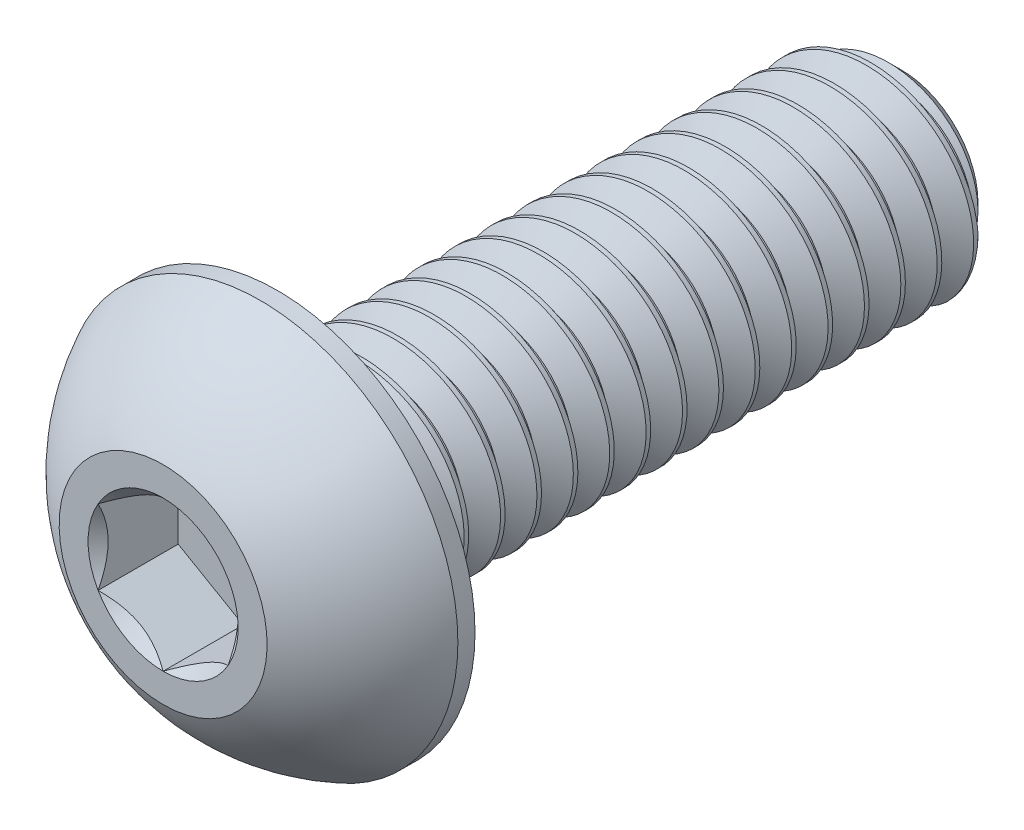
SolidWorks part; units mm, degrees
ref_plane "Front" through (0, 0, 0) normal (0, 0, 1) x (1, 0, 0)
ref_plane "Top" through (0, 0, 0) normal (0, 1, 0) x (1, 0, 0)
ref_plane "Right" through (0, 0, 0) normal (1, 0, 0) x (0, 0, -1)
sketch "Sketch1" plane through (0, 0, 0) normal (1, 0, 0) x (0, 0, -1)
  line L2 (2.2, 2) -> (14.2, 2)
  line L3 (14.2, 2) -> (14.2, 0)
  line L4 (14.2, 0) -> (2.2, 0)
  line L6 (1.87, 3.8) -> (2.2, 3.8) construction
  line L7 (14.2, 2) -> (14.2, -2) construction
  line L8 (0, 0) -> (2.2, 0) construction
  line L9 (2.2, 3.8) -> (2.2, -3.8) construction
  line L11 (2.2, 2) -> (2.2, 0)
  line L13 (0, 1.25) -> (0, -1.25) construction
  line L14 (0, 1.25) -> (0, 2) construction
  line L15 (14.1562, 2.0758) -> (14.5062, 1.4696) construction
  line L16 (14.5062, 1.4696) -> (14.8562, 2.0758) construction
  line L17 (14.8562, 2.0758) -> (14.1562, 2.0758) construction
  line L18 (14.2, 2) -> (14.8125, 2) construction
  line L19 (14.5062, 2.0758) -> (14.5062, 2) construction
  line L20 (14.5062, 2) -> (14.5062, 1.5453) construction
  line L21 (14.5062, 1.5453) -> (14.5062, 1.4696) construction
  line L22 (14.4625, 1.5453) -> (14.55, 1.5453)
  line L23 (14.1781, 2.0379) -> (14.8344, 2.0379)
  line L24 (14.55, 1.5453) -> (14.8344, 2.0379)
  line L25 (14.4625, 1.5453) -> (14.1781, 2.0379)
  line L26 (13.675, 2) -> (14.2, 1.475)
  arc A3 (0, 2) -> (1.87, 3.8) centre (3.7264, 0) cw construction
  point P29 (14.5062, 2.0379)
  point P30 (12.45, -2)
  dimension "D1" = 0.33
  dimension "Pitch" = 0.7
  dimension "D3" = 0.0875
  dimension "D2" = 0.525
  dimension "D4" = 45
  dimension "D5" = 1.75
sketch "Sketch10" plane through (0, 0, 0) normal (1, 0, 0) x (0, 0, -1)
  line L0 (13.675, 2) -> (14.2, 1.475) construction
  line L1 (13.675, 2) -> (14.2, 1.475)
  line L4 (14.2, 2) -> (2.2, 2)
  line L5 (14.2, 0) -> (14.2, 2)
  line L6 (2.2, 0) -> (14.2, 0)
  line L7 (2.2, 2) -> (2.2, 0)
  line L8 (13.675, 2) -> (2.2, 2)
  line L9 (14.2, 0) -> (14.2, 1.475)
  line L10 (2.2, 0) -> (14.2, 0)
  line L11 (2.2, 2) -> (2.2, 0)
  dimension "D1" = 0
revolve "Revolve3" add sketch "Sketch10" angle 360 about L8
sketch "Sketch7" plane through (0, 0, 0) normal (1, 0, 0) x (0, 0, -1)
  line L6 (1.87, 3.8) -> (2.2, 3.8) construction
  line L8 (0, 0) -> (2.2, 0) construction
  line L11 (2.2, 3.8) -> (2.2, -3.8) construction
  line L12 (1.87, 3.8) -> (2.2, 3.8)
  line L13 (0, 0) -> (2.2, 0)
  line L14 (0, 1.25) -> (0, -1.25) construction
  line L15 (2.2, 3.8) -> (2.2, 0)
  line L16 (0, 2) -> (0, 0)
  arc A2 (1.87, 3.8) -> (0, 2) centre (3.7264, 0) ccw construction
  arc A3 (1.87, 3.8) -> (0, 2) centre (3.7264, 0) ccw
revolve "Revolve2" add sketch "Sketch7" angle 360 mid plane about L13
sketch "Sketch5" plane through (0, 0, 0) normal (0, 0, 1) x (1, 0, 0)
  line L1 (1.25, -0.7217) -> (1.25, 0.7217)
  line L2 (1.25, 0.7217) -> (0, 1.4434)
  line L3 (0, 1.4434) -> (-1.25, 0.7217)
  line L4 (-1.25, 0.7217) -> (-1.25, -0.7217)
  line L5 (-1.25, -0.7217) -> (0, -1.4434)
  line L6 (0, -1.4434) -> (1.25, -0.7217)
  circle A0 centre (0, 0) radius 1.25 construction
extrude "Cut-Extrude2" cut sketch "Sketch5" against normal blind 1.54
sketch "Sketch6" plane through (0, 0, 0) normal (0, 0, 1) x (1, 0, 0)
  circle A0 centre (0, 0) radius 1.4434
extrude "Cut-Extrude3" cut sketch "Sketch6" against normal blind 1.54 draft 45
sketch "Sketch9" plane through (0, 0, -2.2) normal (0, 0, -1) x (-1, 0, 0)
  circle A0 centre (0, 0) radius 2 construction
  circle A4 centre (0, 0) radius 2
split "Split1" bodies to split 113 resulting bodies 123 124 split by face at (3.8, 0, -2.2)
sketch "Sketch11" plane through (0, 0, -14.2) normal (0, 0, -1) x (-1, 0, 0)
  circle A0 centre (0, 0) radius 2 construction
  circle A1 centre (0, 0) radius 2
curve "Helix/Spiral1" pitch 0.7 height 14.2 radius 2 centre (0, 0, -14.2) axis (0, 0, 1) start towards (0, 1, 0)
sketch "Sketch12" plane through (0, 0, 0) normal (1, 0, 0) x (0, 0, -1)
  line L0 (14.4625, 1.5453) -> (14.55, 1.5453) construction
  line L1 (14.55, 1.5453) -> (14.8344, 2.0379) construction
  line L2 (14.1781, 2.0379) -> (14.8344, 2.0379) construction
  line L3 (14.4625, 1.5453) -> (14.1781, 2.0379) construction
  line L4 (14.4625, 1.5453) -> (14.55, 1.5453)
  line L5 (14.55, 1.5453) -> (14.8344, 2.0379)
  line L6 (14.1781, 2.0379) -> (14.8344, 2.0379)
  line L7 (14.4625, 1.5453) -> (14.1781, 2.0379)
sweep "Cut-Sweep2" cut profiles "Sketch12" path "Helix/Spiral1" align with end faces yes
extrude "Boss-Extrude1" add sketch "Sketch9" along normal blind 10 draft 45
equation "\"D1@Cut-Extrude2\" = \"Head Ht@Sketch1\" * .7"
equation "\"D1@Sketch1\" = \"Head Ht@Sketch1\" * .15"
equation "\"D1@Cut-Extrude3\" = \"D1@Cut-Extrude2\""
equation "\"D3@Sketch1\" = \"Pitch@Sketch1\" / 8"
equation "\"D2@Sketch1\"=\"Pitch@Sketch1\"*0.75"
equation "\"D3@Helix/Spiral1\" = \"Lg@Sketch1\" + \"Head Ht@Sketch1\""
equation "\"D4@Helix/Spiral1\"=\"pitch@sketch1\""
equation "\"D5@Sketch1\"=\"Pitch@Sketch1\"*2.5"
